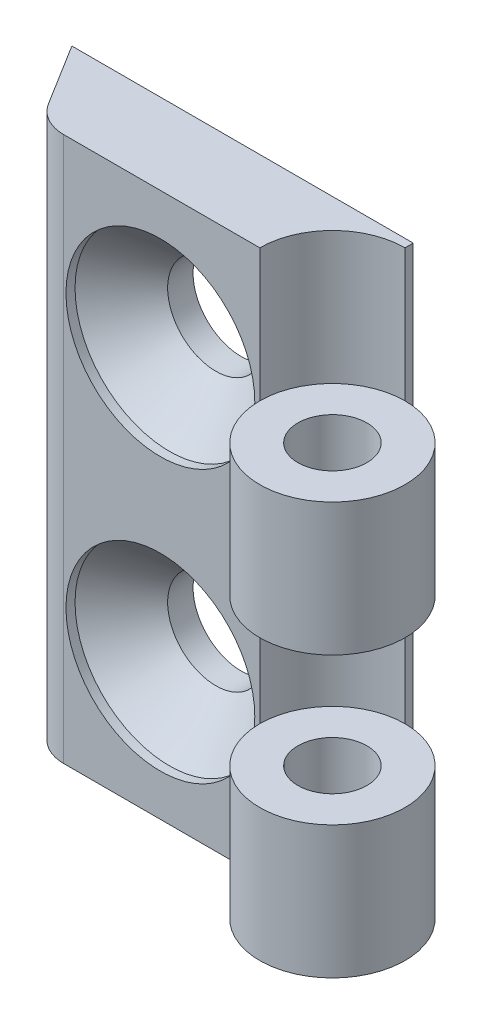
SolidWorks part; units mm, degrees
ref_plane "Front Plane" through (0, 0, 0) normal (0, 0, 1) x (1, 0, 0)
ref_plane "Top Plane" through (0, 0, 0) normal (0, 1, 0) x (1, 0, 0)
ref_plane "Right Plane" through (0, 0, 0) normal (1, 0, 0) x (0, 0, -1)
sketch "Sketch1" plane through (0, 0, 0) normal (0, 1, 0) x (1, 0, 0)
  line L0 (0, 4.45) -> (-18.8, 4.45)
  line L1 (-4, 0) -> (4, 0) construction
  line L2 (-14.8, 0) -> (-4, 0)
  line L4 (-16.6904, 1.0515) -> (-18.8, 4.45)
  line L6 (0, 4.45) -> (0, 4)
  arc A0 (-16.6904, 1.0515) -> (-14.8, 0) centre (-14.8, 2.225) ccw
  circle A1 centre (0, 0) radius 1.9
  circle A2 centre (0, 0) radius 4
  dimension "D2" = 8
  dimension "D6" = 3.8
  dimension "D3" = 4.45
  dimension "D4" = 18.8
  dimension "D5" = 0.45
  dimension "D7" = 10.8
  dimension "D1" = 4
extrude "Boss-Extrude1" add sketch "Sketch1" along normal blind 7.3 contours A2 L0 L2 | A2 L2 A1 | A2 A1 | L2 A2 A1 region at (-10.0662, 0, -2.4053) region at (2.7484, 0, -2.7484)
extrude "Boss-Extrude2" add sketch "Sketch1<3>" along normal blind 30 contours A2 L0 L2 region at (-10.0662, 0, -2.4053)
sketch "Sketch1<3>" plane through (0, 0, 0) normal (0, 1, 0) x (1, 0, 0) same geometry as "Sketch1"
extrude "Boss-Extrude5" add sketch "Sketch1<7>" along normal blind 7.3 from offset 15.4 contours L2 A2 A1 | A2 L2 A1 | A2 A1 region at (2.7484, 0, -2.7484)
sketch "Sketch1<7>" plane through (0, 0, 0) normal (0, 1, 0) x (1, 0, 0) same geometry as "Sketch1"
hole_wizard "CSK for M5 Countersunk Flat Head Screw1" positions "Sketch4" profile "Sketch3" countersink size "M5" standard "ISO" end condition through all
sketch "Sketch4" plane through (0, 0, 0) normal (0, 0, 1) x (1, 0, 0)
  line L3 (-18.8, 30) -> (-18.8, 0) construction
  line L5 (-9.475, 0) -> (-9.475, 30) construction
  line L6 (-14.8, 30) -> (-4, 30) construction
  line L9 (-14.8, 0) -> (-4, 0) construction
  point P0 (-9.475, 22.5)
  point P3 (-9.475, 7.5)
  dimension "D1" = 9.325
  dimension "D2" = 15
  dimension "D3" = 7.5
sketch "Sketch3" plane through (-9.475, 22.5, 0) normal (1, 0, 0) x (0, -1, 0)
  line L0 (0, 0) -> (0, 4.45)
  line L1 (0, 4.45) -> (2.65, 4.45)
  line L2 (2.65, 4.45) -> (2.65, 3.05)
  line L3 (2.65, 3.05) -> (5.2, 0.5)
  line L4 (5.2, 0.5) -> (5.2, 0)
  line L6 (5.2, 0) -> (0, 0)
  line L7 (-2.65, 3.05) -> (-5.2, 0.5) construction
  line L11 (0, -6.35) -> (0, 107.95) construction
  dimension "Thru Hole Dia." = 5.3
  dimension "Thru Hole Depth" = 4.45
  dimension "C'Sink Dia." = 10.4
  dimension "C'Sink Angle" = 90
  dimension "Head Clearance" = 0.5
equation "\"D4@Sketch1\"=22.8-(\"D2@Sketch1\"/2)"
equation "\"D5@Sketch1\"=20-(\"D2@Sketch1\"/2)"
